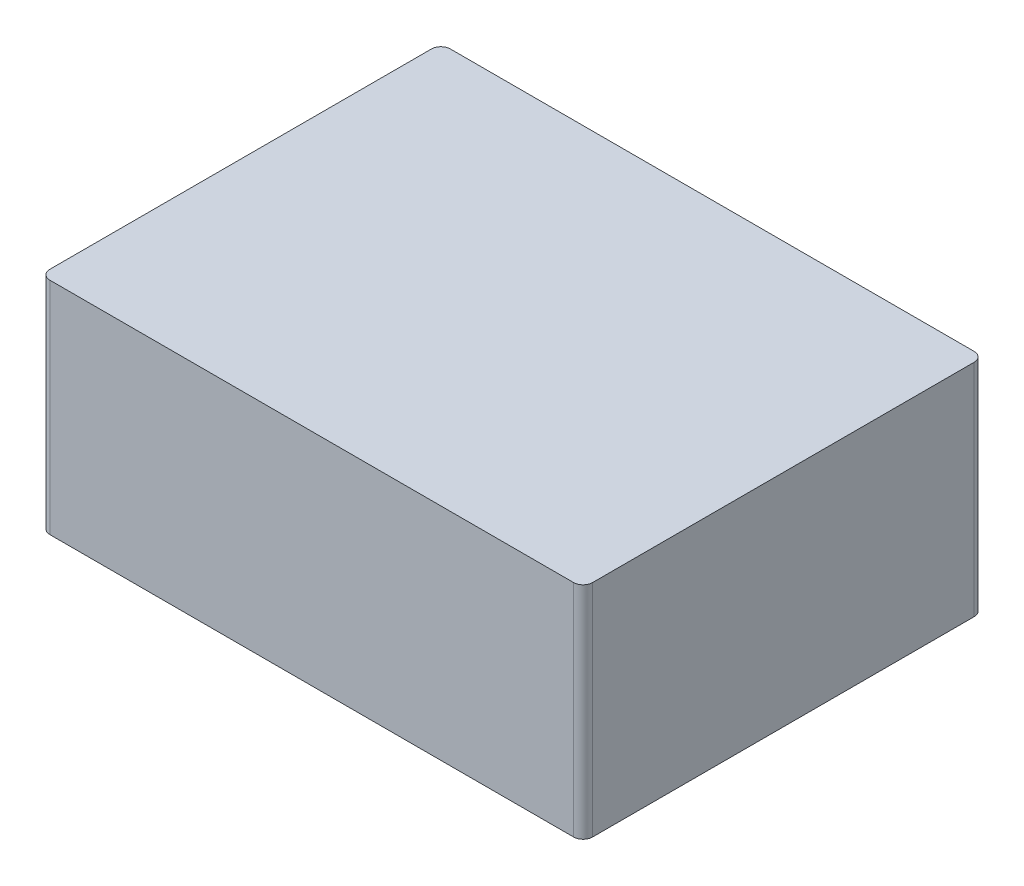
SolidWorks part; units mm, degrees
ref_plane "Front Plane" through (0, 0, 0) normal (0, 0, 1) x (1, 0, 0)
ref_plane "Top Plane" through (0, 0, 0) normal (0, 1, 0) x (1, 0, 0)
ref_plane "Right Plane" through (0, 0, 0) normal (1, 0, 0) x (0, 0, -1)
sketch "Sketch1" plane through (0, 0, 0) normal (0, 1, 0) x (1, 0, 0)
  line L1 (0, 0) -> (114.5, 0)
  line L2 (0, 0) -> (0, 84.5)
  line L3 (0, 84.5) -> (114.5, 84.5)
  line L4 (114.5, 0) -> (114.5, 84.5)
  dimension "D1" = 114.5
  dimension "D2" = 84.5
extrude "Boss-Extrude3" add sketch "Sketch1" along normal blind 46.5
fillet "Fillet2" radius 2 1 edges at (114.5, 23.25, 0)
fillet "Fillet3" radius 2 1 edges at (0, 23.25, 0)
fillet "Fillet4" radius 2 1 edges at (114.5, 23.25, -84.5)
fillet "Fillet5" radius 2 1 edges at (0, 23.25, -84.5)
